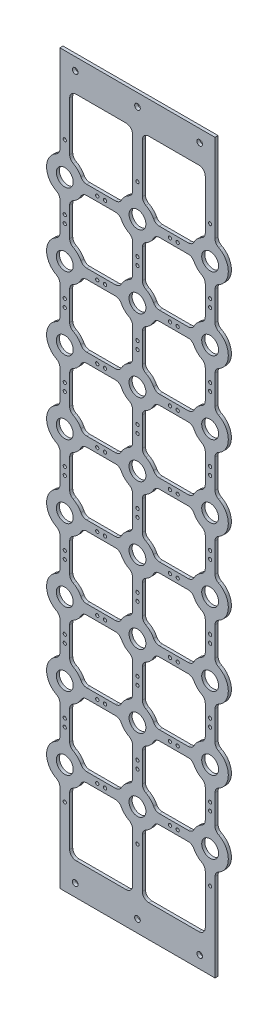
SolidWorks part; units mm, degrees
material "Custom Plastic"
ref_plane "Front Plane" through (0, 0, 0) normal (0, 0, 1) x (1, 0, 0)
ref_plane "Top Plane" through (0, 0, 0) normal (0, 1, 0) x (1, 0, 0)
ref_plane "Right Plane" through (0, 0, 0) normal (1, 0, 0) x (0, 0, -1)
ref_plane "Plane1" through (0, 0, 1.5875) normal (0, 0, 1) x (1, 0, 0)
sketch "Sketch1" plane through (0, 0, 1.5875) normal (0, 0, 1) x (1, 0, 0)
  line L0 (-141, 561) -> (-141, -561)
  line L1 (-141, -561) -> (141, -561)
  line L2 (141, -561) -> (141, 561)
  line L3 (141, 561) -> (-141, 561)
extrude "Boss-Extrude1" add sketch "Sketch1" against normal blind 4.7625
sketch "Sketch2" plane through (0, 0, -3.175) normal (0, 0, -1) x (-1, 0, 0)
  line L0 (141, 511.5) -> (119.5, 511.5)
  line L1 (119.5, 511.5) -> (119.5, 418.9872)
  line L2 (119.5, 365.0128) -> (119.5, 306.9872)
  line L3 (119.5, 253.0128) -> (119.5, 194.9872)
  line L4 (119.5, 141.0128) -> (119.5, 82.9872)
  line L5 (119.5, 29.0128) -> (119.5, -29.0128)
  line L6 (119.5, -82.9872) -> (119.5, -141.0128)
  line L7 (119.5, -194.9872) -> (119.5, -253.0128)
  line L8 (119.5, -306.9872) -> (119.5, -365.0128)
  line L9 (119.5, -418.9872) -> (119.5, -511.5)
  line L10 (119.5, -511.5) -> (141, -511.5)
  line L11 (141, -511.5) -> (141, 511.5)
  arc A0 (119.5, 418.9872) -> (119.5, 365.0128) centre (112, 392) cw
  arc A1 (119.5, 306.9872) -> (119.5, 253.0128) centre (112, 280) cw
  arc A2 (119.5, 194.9872) -> (119.5, 141.0128) centre (112, 168) cw
  arc A3 (119.5, 82.9872) -> (119.5, 29.0128) centre (112, 56) cw
  arc A4 (119.5, -29.0128) -> (119.5, -82.9872) centre (112, -56) cw
  arc A5 (119.5, -141.0128) -> (119.5, -194.9872) centre (112, -168) cw
  arc A6 (119.5, -253.0128) -> (119.5, -306.9872) centre (112, -280) cw
  arc A7 (119.5, -365.0128) -> (119.5, -418.9872) centre (112, -392) cw
extrude "Cut-Extrude1" cut sketch "Sketch2" against normal through all
sketch "Sketch3" plane through (0, 0, -3.175) normal (0, 0, -1) x (-1, 0, 0)
  line L0 (-141, 511.5) -> (-141, -511.5)
  line L1 (-141, -511.5) -> (-119.5, -511.5)
  line L2 (-119.5, -511.5) -> (-119.5, -418.9872)
  line L3 (-119.5, -365.0128) -> (-119.5, -306.9872)
  line L4 (-119.5, -253.0128) -> (-119.5, -194.9872)
  line L5 (-119.5, -141.0128) -> (-119.5, -82.9872)
  line L6 (-119.5, -29.0128) -> (-119.5, 29.0128)
  line L7 (-119.5, 82.9872) -> (-119.5, 141.0128)
  line L8 (-119.5, 194.9872) -> (-119.5, 253.0128)
  line L9 (-119.5, 306.9872) -> (-119.5, 365.0128)
  line L10 (-119.5, 418.9872) -> (-119.5, 511.5)
  line L11 (-119.5, 511.5) -> (-141, 511.5)
  arc A0 (-119.5, -418.9872) -> (-119.5, -365.0128) centre (-112, -392) cw
  arc A1 (-119.5, -306.9872) -> (-119.5, -253.0128) centre (-112, -280) cw
  arc A2 (-119.5, -194.9872) -> (-119.5, -141.0128) centre (-112, -168) cw
  arc A3 (-119.5, -82.9872) -> (-119.5, -29.0128) centre (-112, -56) cw
  arc A4 (-119.5, 29.0128) -> (-119.5, 82.9872) centre (-112, 56) cw
  arc A5 (-119.5, 141.0128) -> (-119.5, 194.9872) centre (-112, 168) cw
  arc A6 (-119.5, 253.0128) -> (-119.5, 306.9872) centre (-112, 280) cw
  arc A7 (-119.5, 365.0128) -> (-119.5, 418.9872) centre (-112, 392) cw
extrude "Cut-Extrude2" cut sketch "Sketch3" against normal through all
sketch "Sketch4" plane through (0, 0, 1.5875) normal (0, 0, 1) x (1, 0, 0)
  line L0 (-26.9872, -399.5) -> (-85.0128, -399.5)
  line L1 (-104.5, -418.9872) -> (-104.5, -511.5)
  line L2 (-104.5, -511.5) -> (-7.5, -511.5)
  line L3 (-7.5, -511.5) -> (-7.5, -418.9872)
  arc A0 (-7.5, -418.9872) -> (-26.9872, -399.5) centre (0, -392) cw
  arc A1 (-85.0128, -399.5) -> (-104.5, -418.9872) centre (-112, -392) cw
extrude "Cut-Extrude3" cut sketch "Sketch4" against normal through all
sketch "Sketch5" plane through (0, 0, 1.5875) normal (0, 0, 1) x (1, 0, 0)
  line L0 (-85.0128, 287.5) -> (-26.9872, 287.5)
  line L1 (-7.5, 306.9872) -> (-7.5, 365.0128)
  line L2 (-26.9872, 384.5) -> (-85.0128, 384.5)
  line L3 (-104.5, 365.0128) -> (-104.5, 306.9872)
  arc A0 (-104.5, 306.9872) -> (-85.0128, 287.5) centre (-112, 280) cw
  arc A1 (-26.9872, 287.5) -> (-7.5, 306.9872) centre (0, 280) cw
  arc A2 (-7.5, 365.0128) -> (-26.9872, 384.5) centre (0, 392) cw
  arc A3 (-85.0128, 384.5) -> (-104.5, 365.0128) centre (-112, 392) cw
extrude "Cut-Extrude4" cut sketch "Sketch5" against normal through all
sketch "Sketch6" plane through (0, 0, 1.5875) normal (0, 0, 1) x (1, 0, 0)
  line L0 (26.9872, -384.5) -> (85.0128, -384.5)
  line L1 (104.5, -365.0128) -> (104.5, -306.9872)
  line L2 (85.0128, -287.5) -> (26.9872, -287.5)
  line L3 (7.5, -306.9872) -> (7.5, -365.0128)
  arc A0 (7.5, -365.0128) -> (26.9872, -384.5) centre (0, -392) cw
  arc A1 (85.0128, -384.5) -> (104.5, -365.0128) centre (112, -392) cw
  arc A2 (104.5, -306.9872) -> (85.0128, -287.5) centre (112, -280) cw
  arc A3 (26.9872, -287.5) -> (7.5, -306.9872) centre (0, -280) cw
extrude "Cut-Extrude5" cut sketch "Sketch6" against normal through all
sketch "Sketch7" plane through (0, 0, 1.5875) normal (0, 0, 1) x (1, 0, 0)
  line L0 (26.9872, -272.5) -> (85.0128, -272.5)
  line L1 (104.5, -253.0128) -> (104.5, -194.9872)
  line L2 (85.0128, -175.5) -> (26.9872, -175.5)
  line L3 (7.5, -194.9872) -> (7.5, -253.0128)
  arc A0 (7.5, -253.0128) -> (26.9872, -272.5) centre (0, -280) cw
  arc A1 (85.0128, -272.5) -> (104.5, -253.0128) centre (112, -280) cw
  arc A2 (104.5, -194.9872) -> (85.0128, -175.5) centre (112, -168) cw
  arc A3 (26.9872, -175.5) -> (7.5, -194.9872) centre (0, -168) cw
extrude "Cut-Extrude6" cut sketch "Sketch7" against normal through all
sketch "Sketch8" plane through (0, 0, 1.5875) normal (0, 0, 1) x (1, 0, 0)
  line L0 (26.9872, -160.5) -> (85.0128, -160.5)
  line L1 (104.5, -141.0128) -> (104.5, -82.9872)
  line L2 (85.0128, -63.5) -> (26.9872, -63.5)
  line L3 (7.5, -82.9872) -> (7.5, -141.0128)
  arc A0 (7.5, -141.0128) -> (26.9872, -160.5) centre (0, -168) cw
  arc A1 (85.0128, -160.5) -> (104.5, -141.0128) centre (112, -168) cw
  arc A2 (104.5, -82.9872) -> (85.0128, -63.5) centre (112, -56) cw
  arc A3 (26.9872, -63.5) -> (7.5, -82.9872) centre (0, -56) cw
extrude "Cut-Extrude7" cut sketch "Sketch8" against normal through all
sketch "Sketch9" plane through (0, 0, 1.5875) normal (0, 0, 1) x (1, 0, 0)
  line L0 (-85.0128, 175.5) -> (-26.9872, 175.5)
  line L1 (-7.5, 194.9872) -> (-7.5, 253.0128)
  line L2 (-26.9872, 272.5) -> (-85.0128, 272.5)
  line L3 (-104.5, 253.0128) -> (-104.5, 194.9872)
  arc A0 (-104.5, 194.9872) -> (-85.0128, 175.5) centre (-112, 168) cw
  arc A1 (-26.9872, 175.5) -> (-7.5, 194.9872) centre (0, 168) cw
  arc A2 (-7.5, 253.0128) -> (-26.9872, 272.5) centre (0, 280) cw
  arc A3 (-85.0128, 272.5) -> (-104.5, 253.0128) centre (-112, 280) cw
extrude "Cut-Extrude8" cut sketch "Sketch9" against normal through all
sketch "Sketch10" plane through (0, 0, 1.5875) normal (0, 0, 1) x (1, 0, 0)
  line L0 (-85.0128, 63.5) -> (-26.9872, 63.5)
  line L1 (-7.5, 82.9872) -> (-7.5, 141.0128)
  line L2 (-26.9872, 160.5) -> (-85.0128, 160.5)
  line L3 (-104.5, 141.0128) -> (-104.5, 82.9872)
  arc A0 (-104.5, 82.9872) -> (-85.0128, 63.5) centre (-112, 56) cw
  arc A1 (-26.9872, 63.5) -> (-7.5, 82.9872) centre (0, 56) cw
  arc A2 (-7.5, 141.0128) -> (-26.9872, 160.5) centre (0, 168) cw
  arc A3 (-85.0128, 160.5) -> (-104.5, 141.0128) centre (-112, 168) cw
extrude "Cut-Extrude9" cut sketch "Sketch10" against normal through all
sketch "Sketch11" plane through (0, 0, 1.5875) normal (0, 0, 1) x (1, 0, 0)
  line L0 (-85.0128, -48.5) -> (-26.9872, -48.5)
  line L1 (-7.5, -29.0128) -> (-7.5, 29.0128)
  line L2 (-26.9872, 48.5) -> (-85.0128, 48.5)
  line L3 (-104.5, 29.0128) -> (-104.5, -29.0128)
  arc A0 (-104.5, -29.0128) -> (-85.0128, -48.5) centre (-112, -56) cw
  arc A1 (-26.9872, -48.5) -> (-7.5, -29.0128) centre (0, -56) cw
  arc A2 (-7.5, 29.0128) -> (-26.9872, 48.5) centre (0, 56) cw
  arc A3 (-85.0128, 48.5) -> (-104.5, 29.0128) centre (-112, 56) cw
extrude "Cut-Extrude10" cut sketch "Sketch11" against normal through all
sketch "Sketch12" plane through (0, 0, 1.5875) normal (0, 0, 1) x (1, 0, 0)
  line L0 (-85.0128, -160.5) -> (-26.9872, -160.5)
  line L1 (-7.5, -141.0128) -> (-7.5, -82.9872)
  line L2 (-26.9872, -63.5) -> (-85.0128, -63.5)
  line L3 (-104.5, -82.9872) -> (-104.5, -141.0128)
  arc A0 (-104.5, -141.0128) -> (-85.0128, -160.5) centre (-112, -168) cw
  arc A1 (-26.9872, -160.5) -> (-7.5, -141.0128) centre (0, -168) cw
  arc A2 (-7.5, -82.9872) -> (-26.9872, -63.5) centre (0, -56) cw
  arc A3 (-85.0128, -63.5) -> (-104.5, -82.9872) centre (-112, -56) cw
extrude "Cut-Extrude11" cut sketch "Sketch12" against normal through all
sketch "Sketch13" plane through (0, 0, 1.5875) normal (0, 0, 1) x (1, 0, 0)
  line L0 (26.9872, -48.5) -> (85.0128, -48.5)
  line L1 (104.5, -29.0128) -> (104.5, 29.0128)
  line L2 (85.0128, 48.5) -> (26.9872, 48.5)
  line L3 (7.5, 29.0128) -> (7.5, -29.0128)
  arc A0 (7.5, -29.0128) -> (26.9872, -48.5) centre (0, -56) cw
  arc A1 (85.0128, -48.5) -> (104.5, -29.0128) centre (112, -56) cw
  arc A2 (104.5, 29.0128) -> (85.0128, 48.5) centre (112, 56) cw
  arc A3 (26.9872, 48.5) -> (7.5, 29.0128) centre (0, 56) cw
extrude "Cut-Extrude12" cut sketch "Sketch13" against normal through all
sketch "Sketch14" plane through (0, 0, 1.5875) normal (0, 0, 1) x (1, 0, 0)
  line L0 (26.9872, 63.5) -> (85.0128, 63.5)
  line L1 (104.5, 82.9872) -> (104.5, 141.0128)
  line L2 (85.0128, 160.5) -> (26.9872, 160.5)
  line L3 (7.5, 141.0128) -> (7.5, 82.9872)
  arc A0 (7.5, 82.9872) -> (26.9872, 63.5) centre (0, 56) cw
  arc A1 (85.0128, 63.5) -> (104.5, 82.9872) centre (112, 56) cw
  arc A2 (104.5, 141.0128) -> (85.0128, 160.5) centre (112, 168) cw
  arc A3 (26.9872, 160.5) -> (7.5, 141.0128) centre (0, 168) cw
extrude "Cut-Extrude13" cut sketch "Sketch14" against normal through all
sketch "Sketch15" plane through (0, 0, 1.5875) normal (0, 0, 1) x (1, 0, 0)
  line L0 (26.9872, 175.5) -> (85.0128, 175.5)
  line L1 (104.5, 194.9872) -> (104.5, 253.0128)
  line L2 (85.0128, 272.5) -> (26.9872, 272.5)
  line L3 (7.5, 253.0128) -> (7.5, 194.9872)
  arc A0 (7.5, 194.9872) -> (26.9872, 175.5) centre (0, 168) cw
  arc A1 (85.0128, 175.5) -> (104.5, 194.9872) centre (112, 168) cw
  arc A2 (104.5, 253.0128) -> (85.0128, 272.5) centre (112, 280) cw
  arc A3 (26.9872, 272.5) -> (7.5, 253.0128) centre (0, 280) cw
extrude "Cut-Extrude14" cut sketch "Sketch15" against normal through all
sketch "Sketch16" plane through (0, 0, 1.5875) normal (0, 0, 1) x (1, 0, 0)
  line L0 (26.9872, 287.5) -> (85.0128, 287.5)
  line L1 (104.5, 306.9872) -> (104.5, 365.0128)
  line L2 (85.0128, 384.5) -> (26.9872, 384.5)
  line L3 (7.5, 365.0128) -> (7.5, 306.9872)
  arc A0 (7.5, 306.9872) -> (26.9872, 287.5) centre (0, 280) cw
  arc A1 (85.0128, 287.5) -> (104.5, 306.9872) centre (112, 280) cw
  arc A2 (104.5, 365.0128) -> (85.0128, 384.5) centre (112, 392) cw
  arc A3 (26.9872, 384.5) -> (7.5, 365.0128) centre (0, 392) cw
extrude "Cut-Extrude15" cut sketch "Sketch16" against normal through all
sketch "Sketch17" plane through (0, 0, 1.5875) normal (0, 0, 1) x (1, 0, 0)
  line L0 (-85.0128, -272.5) -> (-26.9872, -272.5)
  line L1 (-7.5, -253.0128) -> (-7.5, -194.9872)
  line L2 (-26.9872, -175.5) -> (-85.0128, -175.5)
  line L3 (-104.5, -194.9872) -> (-104.5, -253.0128)
  arc A0 (-104.5, -253.0128) -> (-85.0128, -272.5) centre (-112, -280) cw
  arc A1 (-26.9872, -272.5) -> (-7.5, -253.0128) centre (0, -280) cw
  arc A2 (-7.5, -194.9872) -> (-26.9872, -175.5) centre (0, -168) cw
  arc A3 (-85.0128, -175.5) -> (-104.5, -194.9872) centre (-112, -168) cw
extrude "Cut-Extrude16" cut sketch "Sketch17" against normal through all
sketch "Sketch18" plane through (0, 0, 1.5875) normal (0, 0, 1) x (1, 0, 0)
  line L0 (-85.0128, -384.5) -> (-26.9872, -384.5)
  line L1 (-7.5, -365.0128) -> (-7.5, -306.9872)
  line L2 (-26.9872, -287.5) -> (-85.0128, -287.5)
  line L3 (-104.5, -306.9872) -> (-104.5, -365.0128)
  arc A0 (-104.5, -365.0128) -> (-85.0128, -384.5) centre (-112, -392) cw
  arc A1 (-26.9872, -384.5) -> (-7.5, -365.0128) centre (0, -392) cw
  arc A2 (-7.5, -306.9872) -> (-26.9872, -287.5) centre (0, -280) cw
  arc A3 (-85.0128, -287.5) -> (-104.5, -306.9872) centre (-112, -280) cw
extrude "Cut-Extrude17" cut sketch "Sketch18" against normal through all
sketch "Sketch19" plane through (0, 0, 1.5875) normal (0, 0, 1) x (1, 0, 0)
  line L0 (-85.0128, 399.5) -> (-26.9872, 399.5)
  line L1 (-7.5, 418.9872) -> (-7.5, 511.5)
  line L2 (-7.5, 511.5) -> (-104.5, 511.5)
  line L3 (-104.5, 511.5) -> (-104.5, 418.9872)
  arc A0 (-104.5, 418.9872) -> (-85.0128, 399.5) centre (-112, 392) cw
  arc A1 (-26.9872, 399.5) -> (-7.5, 418.9872) centre (0, 392) cw
extrude "Cut-Extrude18" cut sketch "Sketch19" against normal through all
sketch "Sketch20" plane through (0, 0, 1.5875) normal (0, 0, 1) x (1, 0, 0)
  line L0 (7.5, -418.9872) -> (7.5, -511.5)
  line L1 (7.5, -511.5) -> (104.5, -511.5)
  line L2 (104.5, -511.5) -> (104.5, -418.9872)
  line L3 (85.0128, -399.5) -> (26.9872, -399.5)
  arc A0 (26.9872, -399.5) -> (7.5, -418.9872) centre (0, -392) cw
  arc A1 (104.5, -418.9872) -> (85.0128, -399.5) centre (112, -392) cw
extrude "Cut-Extrude19" cut sketch "Sketch20" against normal through all
sketch "Sketch21" plane through (0, 0, -3.175) normal (0, 0, -1) x (-1, 0, 0)
  line L0 (-7.5, 418.9872) -> (-7.5, 511.5)
  line L1 (-7.5, 511.5) -> (-104.5, 511.5)
  line L2 (-104.5, 511.5) -> (-104.5, 418.9872)
  line L3 (-85.0128, 399.5) -> (-26.9872, 399.5)
  arc A0 (-104.5, 418.9872) -> (-85.0128, 399.5) centre (-112, 392) cw
  arc A1 (-26.9872, 399.5) -> (-7.5, 418.9872) centre (0, 392) cw
extrude "Cut-Extrude20" cut sketch "Sketch21" against normal through all
fillet "Fillet1" radius 10 176 edges at (-26.9872, -399.5, -0.7938) (26.9872, 175.5, -0.7938) (119.5, 418.9872, -0.7938) (104.5, 418.9872, -0.7938) (-85.0128, -272.5, -0.7938) (104.5, 511.5, -0.7938) (-119.5, -194.9872, -0.7938) (7.5, 511.5, -0.7938) (119.5, -511.5, -0.7938) (7.5, 418.9872, -0.7938) (26.9872, 287.5, -0.7938) (26.9872, 399.5, -0.7938) (-85.0128, -384.5, -0.7938) (-7.5, 511.5, -0.7938) (104.5, -511.5, -0.7938) (-104.5, 511.5, -0.7938) (-119.5, 253.0128, -0.7938) (-104.5, 418.9872, -0.7938) (119.5, -29.0128, -0.7938) (-85.0128, 399.5, -0.7938) (85.0128, 160.5, -0.7938) (-26.9872, 399.5, -0.7938) (85.0128, 272.5, -0.7938) (-7.5, 418.9872, -0.7938) (85.0128, 384.5, -0.7938) (-85.0128, 384.5, -0.7938) (-26.9872, -175.5, -0.7938) (-104.5, 365.0128, -0.7938) (-26.9872, -287.5, -0.7938) (-104.5, 306.9872, -0.7938) (85.0128, -399.5, -0.7938) (-85.0128, 287.5, -0.7938) (-119.5, -418.9872, -0.7938) (-26.9872, 287.5, -0.7938) (-119.5, 29.0128, -0.7938) (-7.5, 306.9872, -0.7938) (-119.5, 511.5, -0.7938) (-7.5, 365.0128, -0.7938) (119.5, 194.9872, -0.7938) (-26.9872, 384.5, -0.7938) (119.5, -253.0128, -0.7938) (26.9872, -287.5, -0.7938) (104.5, 82.9872, -0.7938) (7.5, -306.9872, -0.7938) (7.5, 253.0128, -0.7938) (7.5, -365.0128, -0.7938) (104.5, 194.9872, -0.7938) (26.9872, -384.5, -0.7938) (7.5, 365.0128, -0.7938) (85.0128, -384.5, -0.7938) (104.5, 306.9872, -0.7938) (104.5, -365.0128, -0.7938) (-104.5, -194.9872, -0.7938) (104.5, -306.9872, -0.7938) (-7.5, -253.0128, -0.7938) (85.0128, -287.5, -0.7938) (-104.5, -306.9872, -0.7938) (26.9872, -175.5, -0.7938) (-7.5, -365.0128, -0.7938) (7.5, -194.9872, -0.7938) (-7.5, -511.5, -0.7938) (7.5, -253.0128, -0.7938) (-104.5, -418.9872, -0.7938) (26.9872, -272.5, -0.7938) (7.5, -418.9872, -0.7938) (85.0128, -272.5, -0.7938) (-141, -511.5, -0.7938) (104.5, -253.0128, -0.7938) (-119.5, -306.9872, -0.7938) (104.5, -194.9872, -0.7938) (-119.5, -82.9872, -0.7938) (85.0128, -175.5, -0.7938) (-119.5, 141.0128, -0.7938) (26.9872, -63.5, -0.7938) (-119.5, 365.0128, -0.7938) (7.5, -82.9872, -0.7938) (141, 511.5, -0.7938) (7.5, -141.0128, -0.7938) (119.5, 306.9872, -0.7938) (26.9872, -160.5, -0.7938) (119.5, 82.9872, -0.7938) (85.0128, -160.5, -0.7938) (119.5, -141.0128, -0.7938) (104.5, -141.0128, -0.7938) (119.5, -365.0128, -0.7938) (104.5, -82.9872, -0.7938) (85.0128, 63.5, -0.7938) (85.0128, -63.5, -0.7938) (104.5, 141.0128, -0.7938) (-85.0128, 272.5, -0.7938) (26.9872, 272.5, -0.7938) (-104.5, 253.0128, -0.7938) (7.5, 194.9872, -0.7938) (-104.5, 194.9872, -0.7938) (85.0128, 175.5, -0.7938) (-85.0128, 175.5, -0.7938) (104.5, 253.0128, -0.7938) (-26.9872, 175.5, -0.7938) (26.9872, 384.5, -0.7938) (-7.5, 194.9872, -0.7938) (7.5, 306.9872, -0.7938) (-7.5, 253.0128, -0.7938) (85.0128, 287.5, -0.7938) (-26.9872, 272.5, -0.7938) (104.5, 365.0128, -0.7938) (-85.0128, 160.5, -0.7938) (-85.0128, -175.5, -0.7938) (-104.5, 141.0128, -0.7938) (-104.5, -253.0128, -0.7938) (-104.5, 82.9872, -0.7938) (-26.9872, -272.5, -0.7938) (-85.0128, 63.5, -0.7938) (-7.5, -194.9872, -0.7938) (-26.9872, 63.5, -0.7938) (-85.0128, -287.5, -0.7938) (-7.5, 82.9872, -0.7938) (-104.5, -365.0128, -0.7938) (-7.5, 141.0128, -0.7938) (-26.9872, -384.5, -0.7938) (-26.9872, 160.5, -0.7938) (-7.5, -306.9872, -0.7938) (-85.0128, 48.5, -0.7938) (-104.5, -511.5, -0.7938) (-104.5, 29.0128, -0.7938) (-7.5, -418.9872, -0.7938) (-104.5, -29.0128, -0.7938) (-85.0128, -399.5, -0.7938) (-85.0128, -48.5, -0.7938) (104.5, -418.9872, -0.7938) (-26.9872, -48.5, -0.7938) (26.9872, -399.5, -0.7938) (-7.5, -29.0128, -0.7938) (7.5, -511.5, -0.7938) (-7.5, 29.0128, -0.7938) (141, -511.5, -0.7938) (-26.9872, 48.5, -0.7938) (-119.5, -511.5, -0.7938) (-85.0128, -63.5, -0.7938) (-119.5, -365.0128, -0.7938) (-104.5, -82.9872, -0.7938) (-119.5, -253.0128, -0.7938) (-104.5, -141.0128, -0.7938) (-119.5, -141.0128, -0.7938) (-85.0128, -160.5, -0.7938) (-119.5, -29.0128, -0.7938) (-26.9872, -160.5, -0.7938) (-119.5, 82.9872, -0.7938) (-7.5, -141.0128, -0.7938) (-119.5, 194.9872, -0.7938) (-7.5, -82.9872, -0.7938) (-119.5, 306.9872, -0.7938) (-26.9872, -63.5, -0.7938) (-119.5, 418.9872, -0.7938) (26.9872, 48.5, -0.7938) (-141, 511.5, -0.7938) (7.5, 29.0128, -0.7938) (119.5, 511.5, -0.7938) (7.5, -29.0128, -0.7938) (119.5, 365.0128, -0.7938) (26.9872, -48.5, -0.7938) (119.5, 253.0128, -0.7938) (85.0128, -48.5, -0.7938) (119.5, 141.0128, -0.7938) (104.5, -29.0128, -0.7938) (119.5, 29.0128, -0.7938) (104.5, 29.0128, -0.7938) (119.5, -82.9872, -0.7938) (85.0128, 48.5, -0.7938) (119.5, -194.9872, -0.7938) (26.9872, 160.5, -0.7938) (119.5, -306.9872, -0.7938) (7.5, 141.0128, -0.7938) (119.5, -418.9872, -0.7938) (7.5, 82.9872, -0.7938) (85.0128, 399.5, -0.7938) (26.9872, 63.5, -0.7938) tangent propagation no
sketch "Sketch26" plane through (0, 0, 1.5875) normal (0, 0, 1) x (1, 0, 0)
  line L0 (-104.5, 501.5) -> (-104.5, 425.7418) construction
  line L1 (-33.7418, 384.5) -> (-78.2582, 384.5) construction
  circle A0 centre (-112, 442) radius 2.4892
  circle A2 centre (0, 442) radius 2.4892
  circle A3 centre (112, 442) radius 2.4892
  circle A4 centre (-112, 342) radius 2.4892
  circle A5 centre (0, 342) radius 2.4892
  circle A6 centre (112, 342) radius 2.4892
  circle A7 centre (-112, 330) radius 2.4892
  circle A11 centre (0, 330) radius 2.4892
  circle A12 centre (112, 330) radius 2.4892
  circle A19 centre (0, 230) radius 2.4892
  circle A20 centre (-112, 230) radius 2.4892
  circle A21 centre (112, 230) radius 2.4892
  circle A22 centre (-112, 218) radius 2.4892
  circle A24 centre (0, 218) radius 2.4892
  circle A25 centre (112, 218) radius 2.4892
  circle A26 centre (-112, 118) radius 2.4892
  circle A27 centre (0, 118) radius 2.4892
  circle A28 centre (112, 118) radius 2.4892
  circle A29 centre (-112, 106) radius 2.4892
  circle A30 centre (112, 106) radius 2.4892
  circle A31 centre (0, 106) radius 2.4892
  circle A32 centre (0, 6) radius 2.4892
  circle A33 centre (0, -6) radius 2.4892
  circle A34 centre (-112, 6) radius 2.4892
  circle A35 centre (112, 6) radius 2.4892
  circle A36 centre (-112, -6) radius 2.4892
  circle A37 centre (112, -6) radius 2.4892
  circle A38 centre (0, -218) radius 2.4892
  circle A39 centre (112, -218) radius 2.4892
  circle A40 centre (0, -230) radius 2.4892
  circle A41 centre (-112, -218) radius 2.4892
  circle A42 centre (-112, -230) radius 2.4892
  circle A43 centre (112, -230) radius 2.4892
  circle A44 centre (0, -118) radius 2.4892
  circle A45 centre (-112, -118) radius 2.4892
  circle A46 centre (112, -118) radius 2.4892
  circle A47 centre (0, -106) radius 2.4892
  circle A48 centre (-112, -106) radius 2.4892
  circle A49 centre (112, -106) radius 2.4892
  circle A50 centre (-112, -330) radius 2.4892
  circle A51 centre (0, -330) radius 2.4892
  circle A52 centre (112, -342) radius 2.4892
  circle A53 centre (112, -330) radius 2.4892
  circle A54 centre (0, -342) radius 2.4892
  circle A55 centre (-112, -342) radius 2.4892
  circle A56 centre (112, -442) radius 2.4892
  circle A60 centre (0, -442) radius 2.4892
  circle A61 centre (-112, -442) radius 2.4892
  circle A62 centre (-62, 392) radius 2.4892
  circle A63 centre (-50, 392) radius 2.4892
  circle A65 centre (50, 392) radius 2.4892
  circle A66 centre (62, 392) radius 2.4892
  circle A68 centre (62, 168) radius 2.4892
  circle A69 centre (-62, 168) radius 2.4892
  circle A70 centre (50, 168) radius 2.4892
  circle A71 centre (-50, 168) radius 2.4892
  circle A76 centre (-50, 280) radius 2.4892
  circle A77 centre (62, 280) radius 2.4892
  circle A78 centre (-62, 280) radius 2.4892
  circle A79 centre (50, 280) radius 2.4892
  circle A80 centre (62, 56) radius 2.4892
  circle A81 centre (-62, 56) radius 2.4892
  circle A82 centre (50, 56) radius 2.4892
  circle A83 centre (-50, 56) radius 2.4892
  circle A84 centre (62, -56) radius 2.4892
  circle A85 centre (-62, -56) radius 2.4892
  circle A86 centre (-50, -56) radius 2.4892
  circle A87 centre (50, -56) radius 2.4892
  circle A88 centre (62, -168) radius 2.4892
  circle A89 centre (-50, -168) radius 2.4892
  circle A90 centre (-62, -168) radius 2.4892
  circle A91 centre (50, -168) radius 2.4892
  circle A92 centre (-50, -280) radius 2.4892
  circle A93 centre (-62, -280) radius 2.4892
  circle A94 centre (62, -280) radius 2.4892
  circle A95 centre (50, -280) radius 2.4892
  circle A96 centre (-50, -392) radius 2.4892
  circle A97 centre (62, -392) radius 2.4892
  circle A98 centre (-62, -392) radius 2.4892
  circle A99 centre (50, -392) radius 2.4892
  dimension "D13" = 4.9784
  dimension "D14" = 4.9784
  dimension "small_screw_clearance" = 4.9784
  dimension "D12" = 4.9784
  dimension "D15" = 4.9784
  dimension "D16" = 4.9784
  dimension "D17" = 4.9784
  dimension "D18" = 4.9784
  dimension "D19" = 4.9784
  dimension "D20" = 4.9784
  dimension "D21" = 4.9784
  dimension "D22" = 4.9784
  dimension "D23" = 4.9784
  dimension "D24" = 4.9784
  dimension "D25" = 4.9784
  dimension "D26" = 4.9784
  dimension "D27" = 4.9784
  dimension "D28" = 4.9784
  dimension "D29" = 4.9784
  dimension "D30" = 4.9784
  dimension "D31" = 4.9784
  dimension "D32" = 4.9784
  dimension "D33" = 4.9784
  dimension "D34" = 4.9784
  dimension "D35" = 4.9784
  dimension "D36" = 4.9784
  dimension "D37" = 4.9784
  dimension "D38" = 4.9784
  dimension "D39" = 4.9784
  dimension "D40" = 4.9784
  dimension "D41" = 4.9784
  dimension "D42" = 4.9784
  dimension "D43" = 4.9784
  dimension "D44" = 4.9784
  dimension "D45" = 4.9784
  dimension "D46" = 4.9784
  dimension "D47" = 4.9784
  dimension "D48" = 4.9784
  dimension "D49" = 4.9784
  dimension "D50" = 4.9784
  dimension "D51" = 4.9784
  dimension "D52" = 4.9784
  dimension "D53" = 4.9784
  dimension "D54" = 4.9784
  dimension "D55" = 4.9784
  dimension "D56" = 4.9784
  dimension "D57" = 4.9784
  dimension "D58" = 4.9784
  dimension "D59" = 4.9784
  dimension "D60" = 4.9784
  dimension "D61" = 4.9784
  dimension "D62" = 4.9784
  dimension "D63" = 4.9784
  dimension "D64" = 4.9784
  dimension "D65" = 4.9784
  dimension "D66" = 4.9784
  dimension "D67" = 4.9784
  dimension "D68" = 4.9784
  dimension "D69" = 4.9784
  dimension "D70" = 4.9784
  dimension "D71" = 4.9784
  dimension "D72" = 4.9784
  dimension "D73" = 4.9784
  dimension "D74" = 4.9784
  dimension "D75" = 4.9784
  dimension "D76" = 4.9784
  dimension "D77" = 4.9784
  dimension "D78" = 4.9784
  dimension "D79" = 4.9784
  dimension "D80" = 4.9784
  dimension "D81" = 4.9784
  dimension "D82" = 4.9784
  dimension "D83" = 4.9784
  dimension "D84" = 4.9784
  dimension "D85" = 4.9784
  dimension "D86" = 4.9784
  dimension "D87" = 4.9784
  dimension "D88" = 4.9784
  dimension "D89" = 4.9784
  dimension "D90" = 4.9784
  dimension "D2" = 7.5
  dimension "D7" = 7.5
  dimension "D10" = 12
extrude "Cut-Extrude21" cut sketch "Sketch26" against normal blind 10
sketch "Sketch27" plane through (0, 0, 1.5875) normal (0, 0, 1) x (1, 0, 0)
  circle A1 centre (-95.95, 541.95) radius 4.3688
  circle A3 centre (0, 541.95) radius 4.3688
  circle A5 centre (95.95, 541.95) radius 4.3688
  circle A7 centre (-95.95, -541.95) radius 4.3688
  circle A9 centre (0, -541.95) radius 4.3688
  circle A11 centre (95.95, -541.95) radius 4.3688
  dimension "D1" = 8.7376
  dimension "D2" = 8.7376
  dimension "D3" = 8.7376
  dimension "D4" = 8.7376
  dimension "D5" = 8.7376
  dimension "D6" = 8.7376
sketch "Sketch28" plane through (0, 0, 1.5875) normal (0, 0, 1) x (1, 0, 0)
  circle A0 centre (-112, 392) radius 13
  circle A1 centre (0, 392) radius 13
  circle A2 centre (112, 392) radius 13
  circle A3 centre (-112, 280) radius 13
  circle A4 centre (0, 280) radius 13
  circle A5 centre (112, 280) radius 13
  circle A6 centre (-112, 168) radius 13
  circle A7 centre (0, 168) radius 13
  circle A8 centre (112, 168) radius 13
  circle A9 centre (-112, 56) radius 13
  circle A10 centre (0, 56) radius 13
  circle A11 centre (112, 56) radius 13
  circle A12 centre (-112, -56) radius 13
  circle A13 centre (0, -56) radius 13
  circle A14 centre (112, -56) radius 13
  circle A15 centre (-112, -168) radius 13
  circle A16 centre (0, -168) radius 13
  circle A17 centre (112, -168) radius 13
  circle A18 centre (-112, -280) radius 13
  circle A19 centre (0, -280) radius 13
  circle A20 centre (112, -280) radius 13
  circle A21 centre (-112, -392) radius 13
  circle A22 centre (0, -392) radius 13
  circle A23 centre (112, -392) radius 13
  dimension "D1" = 26
  dimension "D2" = 26
  dimension "D3" = 26
  dimension "D4" = 26
  dimension "D5" = 26
  dimension "D6" = 26
  dimension "D7" = 26
  dimension "D8" = 26
  dimension "D9" = 26
  dimension "D10" = 26
  dimension "D11" = 26
  dimension "D12" = 26
  dimension "D13" = 26
  dimension "D14" = 26
  dimension "D15" = 26
  dimension "D16" = 26
  dimension "D17" = 26
  dimension "D18" = 26
  dimension "D19" = 26
  dimension "D20" = 26
  dimension "D21" = 26
  dimension "D22" = 26
  dimension "D23" = 26
  dimension "D24" = 26
extrude "Cut-Extrude23" cut sketch "Sketch28" against normal blind 10
extrude "Cut-Extrude22" cut sketch "Sketch27" against normal through all
sketch "Sketch29" plane through (0, 0, 1.5875) normal (0, 0, 1) x (1, 0, 0)
  line L0 (-129.5, -511.5) -> (-131, -511.5) construction
  line L1 (-129.5, -511.5) -> (-131, -511.5)
  line L2 (-141, -521.5) -> (-141, -561) construction
  line L3 (-141, -521.5) -> (-141, -561)
  line L4 (-141, -561) -> (141, -561) construction
  line L5 (-141, -561) -> (-119.5, -561)
  line L6 (-119.5, -501.5) -> (-119.5, -561)
  line L7 (141, -561) -> (141, -521.5) construction
  line L8 (141, -561) -> (141, -521.5)
  line L9 (131, -511.5) -> (129.5, -511.5) construction
  line L10 (131, -511.5) -> (129.5, -511.5)
  line L11 (119.5, -501.5) -> (119.5, -561)
  line L12 (119.5, -561) -> (141, -561)
  arc A0 (-129.5, -511.5) -> (-119.5, -501.5) centre (-129.5, -501.5) ccw construction
  arc A1 (-129.5, -511.5) -> (-119.5, -501.5) centre (-129.5, -501.5) ccw
  arc A2 (-131, -511.5) -> (-141, -521.5) centre (-131, -521.5) ccw construction
  arc A3 (-131, -511.5) -> (-141, -521.5) centre (-131, -521.5) ccw
  arc A4 (141, -521.5) -> (131, -511.5) centre (131, -521.5) ccw construction
  arc A5 (141, -521.5) -> (131, -511.5) centre (131, -521.5) ccw
  arc A6 (119.5, -501.5) -> (129.5, -511.5) centre (129.5, -501.5) ccw construction
  arc A7 (119.5, -501.5) -> (129.5, -511.5) centre (129.5, -501.5) ccw
extrude "Cut-Extrude24" cut sketch "Sketch29" against normal blind 10
sketch "Sketch30" plane through (0, 0, 1.5875) normal (0, 0, 1) x (1, 0, 0)
  line L0 (141, 561) -> (-141, 561) construction
  line L1 (141, 561) -> (119.5, 561)
  line L2 (-141, 561) -> (-141, 521.5) construction
  line L3 (-141, 561) -> (-141, 521.5)
  line L4 (-119.5, 501.5) -> (-119.5, 561)
  line L5 (141, 521.5) -> (141, 561) construction
  line L6 (141, 521.5) -> (141, 561)
  line L7 (129.5, 511.5) -> (131, 511.5) construction
  line L8 (129.5, 511.5) -> (131, 511.5)
  line L9 (119.5, 501.5) -> (119.5, 561)
  line L10 (-119.5, 561) -> (-141, 561)
  line L11 (-131, 511.5) -> (-129.5, 511.5) construction
  line L12 (-131, 511.5) -> (-129.5, 511.5)
  arc A0 (-141, 521.5) -> (-131, 511.5) centre (-131, 521.5) ccw construction
  arc A1 (-141, 521.5) -> (-131, 511.5) centre (-131, 521.5) ccw
  arc A2 (-119.5, 501.5) -> (-129.5, 511.5) centre (-129.5, 501.5) ccw construction
  arc A3 (-119.5, 501.5) -> (-129.5, 511.5) centre (-129.5, 501.5) ccw
  arc A4 (131, 511.5) -> (141, 521.5) centre (131, 521.5) ccw construction
  arc A5 (131, 511.5) -> (141, 521.5) centre (131, 521.5) ccw
  arc A6 (129.5, 511.5) -> (119.5, 501.5) centre (129.5, 501.5) ccw construction
  arc A7 (129.5, 511.5) -> (119.5, 501.5) centre (129.5, 501.5) ccw
extrude "Cut-Extrude25" cut sketch "Sketch30" against normal blind 10
equation "\"D13@Sketch26\"= \"small_screw_clearance@Sketch26\""
equation "\"D14@Sketch26\"= \"D13@Sketch26\""
equation "\"D12@Sketch26\"= \"small_screw_clearance@Sketch26\""
equation "\"D15@Sketch26\"= \"small_screw_clearance@Sketch26\""
equation "\"D16@Sketch26\"= \"small_screw_clearance@Sketch26\""
equation "\"D17@Sketch26\"= \"small_screw_clearance@Sketch26\""
equation "\"D18@Sketch26\"= \"small_screw_clearance@Sketch26\""
equation "\"D19@Sketch26\"= \"small_screw_clearance@Sketch26\""
equation "\"D20@Sketch26\"= \"small_screw_clearance@Sketch26\""
equation "\"D21@Sketch26\"= \"small_screw_clearance@Sketch26\""
equation "\"D26@Sketch26\"= \"small_screw_clearance@Sketch26\""
equation "\"D23@Sketch26\"= \"small_screw_clearance@Sketch26\""
equation "\"D22@Sketch26\"= \"small_screw_clearance@Sketch26\""
equation "\"D24@Sketch26\"= \"small_screw_clearance@Sketch26\""
equation "\"D25@Sketch26\"= \"small_screw_clearance@Sketch26\""
equation "\"D27@Sketch26\"= \"small_screw_clearance@Sketch26\""
equation "\"D28@Sketch26\"= \"small_screw_clearance@Sketch26\""
equation "\"D29@Sketch26\"= \"small_screw_clearance@Sketch26\""
equation "\"D30@Sketch26\"= \"small_screw_clearance@Sketch26\""
equation "\"D31@Sketch26\"= \"small_screw_clearance@Sketch26\""
equation "\"D33@Sketch26\"= \"small_screw_clearance@Sketch26\""
equation "\"D32@Sketch26\"= \"small_screw_clearance@Sketch26\""
equation "\"D34@Sketch26\"= \"small_screw_clearance@Sketch26\""
equation "\"D35@Sketch26\"= \"small_screw_clearance@Sketch26\""
equation "\"D36@Sketch26\"= \"small_screw_clearance@Sketch26\""
equation "\"D37@Sketch26\"= \"small_screw_clearance@Sketch26\""
equation "\"D38@Sketch26\"= \"small_screw_clearance@Sketch26\""
equation "\"D39@Sketch26\"= \"small_screw_clearance@Sketch26\""
equation "\"D40@Sketch26\"= \"small_screw_clearance@Sketch26\""
equation "\"D41@Sketch26\"= \"small_screw_clearance@Sketch26\""
equation "\"D42@Sketch26\"= \"small_screw_clearance@Sketch26\""
equation "\"D43@Sketch26\"= \"small_screw_clearance@Sketch26\""
equation "\"D44@Sketch26\"= \"small_screw_clearance@Sketch26\""
equation "\"D45@Sketch26\"= \"small_screw_clearance@Sketch26\""
equation "\"D46@Sketch26\"= \"small_screw_clearance@Sketch26\""
equation "\"D47@Sketch26\"= \"small_screw_clearance@Sketch26\""
equation "\"D48@Sketch26\"= \"small_screw_clearance@Sketch26\""
equation "\"D49@Sketch26\"= \"small_screw_clearance@Sketch26\""
equation "\"D50@Sketch26\"= \"small_screw_clearance@Sketch26\""
equation "\"D51@Sketch26\"= \"small_screw_clearance@Sketch26\""
equation "\"D52@Sketch26\"= \"small_screw_clearance@Sketch26\""
equation "\"D53@Sketch26\"= \"small_screw_clearance@Sketch26\""
equation "\"D54@Sketch26\"= \"small_screw_clearance@Sketch26\""
equation "\"D55@Sketch26\"= \"small_screw_clearance@Sketch26\""
equation "\"D56@Sketch26\"= \"small_screw_clearance@Sketch26\""
equation "\"D57@Sketch26\"= \"small_screw_clearance@Sketch26\""
equation "\"D58@Sketch26\"= \"small_screw_clearance@Sketch26\""
equation "\"D59@Sketch26\"= \"small_screw_clearance@Sketch26\""
equation "\"D60@Sketch26\"= \"small_screw_clearance@Sketch26\""
equation "\"D61@Sketch26\"= \"small_screw_clearance@Sketch26\""
equation "\"D63@Sketch26\"= \"small_screw_clearance@Sketch26\""
equation "\"D62@Sketch26\"= \"small_screw_clearance@Sketch26\""
equation "\"D64@Sketch26\"= \"small_screw_clearance@Sketch26\""
equation "\"D65@Sketch26\"= \"small_screw_clearance@Sketch26\""
equation "\"D66@Sketch26\"= \"small_screw_clearance@Sketch26\""
equation "\"D67@Sketch26\"= \"small_screw_clearance@Sketch26\""
equation "\"D68@Sketch26\"= \"small_screw_clearance@Sketch26\""
equation "\"D69@Sketch26\"= \"small_screw_clearance@Sketch26\""
equation "\"D70@Sketch26\"= \"small_screw_clearance@Sketch26\""
equation "\"D71@Sketch26\"= \"small_screw_clearance@Sketch26\""
equation "\"D72@Sketch26\"= \"small_screw_clearance@Sketch26\""
equation "\"D73@Sketch26\"= \"small_screw_clearance@Sketch26\""
equation "\"D74@Sketch26\"= \"small_screw_clearance@Sketch26\""
equation "\"D75@Sketch26\"= \"small_screw_clearance@Sketch26\""
equation "\"D76@Sketch26\"= \"small_screw_clearance@Sketch26\""
equation "\"D77@Sketch26\"= \"small_screw_clearance@Sketch26\""
equation "\"D78@Sketch26\"= \"small_screw_clearance@Sketch26\""
equation "\"D79@Sketch26\"= \"small_screw_clearance@Sketch26\""
equation "\"D80@Sketch26\"= \"small_screw_clearance@Sketch26\""
equation "\"D81@Sketch26\"= \"small_screw_clearance@Sketch26\""
equation "\"D82@Sketch26\"= \"small_screw_clearance@Sketch26\""
equation "\"D83@Sketch26\"= \"small_screw_clearance@Sketch26\""
equation "\"D84@Sketch26\"= \"small_screw_clearance@Sketch26\""
equation "\"D85@Sketch26\"= \"small_screw_clearance@Sketch26\""
equation "\"D86@Sketch26\"= \"small_screw_clearance@Sketch26\""
equation "\"D87@Sketch26\"= \"small_screw_clearance@Sketch26\""
equation "\"D88@Sketch26\"= \"small_screw_clearance@Sketch26\""
equation "\"D89@Sketch26\"= \"small_screw_clearance@Sketch26\""
equation "\"D90@Sketch26\"= \"small_screw_clearance@Sketch26\""
equation "\"D2@Sketch27\"= \"D1@Sketch27\""
equation "\"D3@Sketch27\"= \"D1@Sketch27\""
equation "\"D4@Sketch27\"= \"D1@Sketch27\""
equation "\"D5@Sketch27\"= \"D1@Sketch27\""
equation "\"D6@Sketch27\"= \"D1@Sketch27\""
equation "\"D2@Sketch28\"= \"D1@Sketch28\""
equation "\"D3@Sketch28\"= \"D1@Sketch28\""
equation "\"D4@Sketch28\"= \"D1@Sketch28\""
equation "\"D5@Sketch28\"= \"D1@Sketch28\""
equation "\"D6@Sketch28\"= \"D1@Sketch28\""
equation "\"D7@Sketch28\"= \"D1@Sketch28\""
equation "\"D8@Sketch28\"= \"D1@Sketch28\""
equation "\"D9@Sketch28\"= \"D1@Sketch28\""
equation "\"D10@Sketch28\"= \"D1@Sketch28\""
equation "\"D11@Sketch28\"= \"D1@Sketch28\""
equation "\"D12@Sketch28\"= \"D1@Sketch28\""
equation "\"D13@Sketch28\"= \"D1@Sketch28\""
equation "\"D14@Sketch28\"= \"D1@Sketch28\""
equation "\"D15@Sketch28\"= \"D1@Sketch28\""
equation "\"D16@Sketch28\"= \"D1@Sketch28\""
equation "\"D17@Sketch28\"= \"D1@Sketch28\""
equation "\"D18@Sketch28\"= \"D1@Sketch28\""
equation "\"D19@Sketch28\"= \"D1@Sketch28\""
equation "\"D20@Sketch28\"= \"D1@Sketch28\""
equation "\"D21@Sketch28\"= \"D1@Sketch28\""
equation "\"D22@Sketch28\"= \"D1@Sketch28\""
equation "\"D23@Sketch28\"= \"D1@Sketch28\""
equation "\"D24@Sketch28\"= \"D1@Sketch28\""
